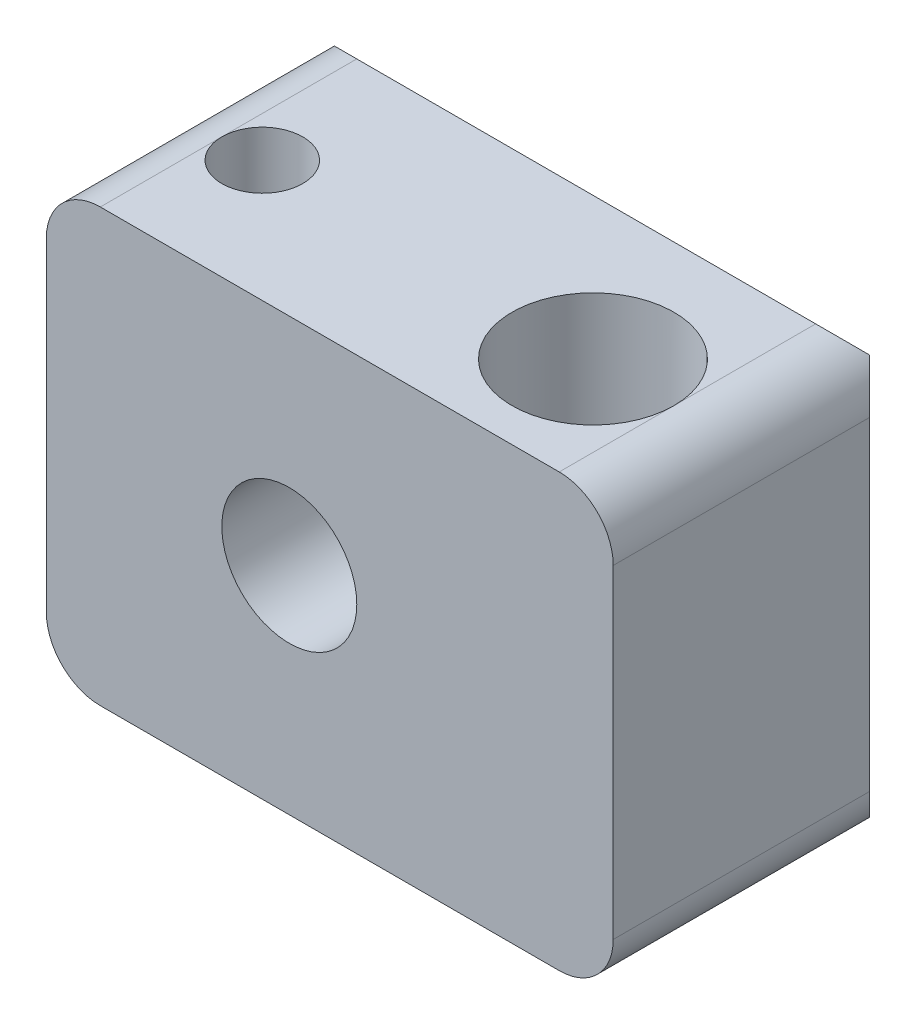
SolidWorks part; units mm, degrees
ref_plane "Front Plane" through (0, 0, 0) normal (0, 0, 1) x (1, 0, 0)
ref_plane "Top Plane" through (0, 0, 0) normal (0, 1, 0) x (1, 0, 0)
ref_plane "Right Plane" through (0, 0, 0) normal (1, 0, 0) x (0, 0, -1)
ref_plane "Plane1" through (0, 0, 0) normal (0, 0, -1) x (-1, 0, 0)
sketch "Sketch1" plane through (0, 0, 0) normal (0, 0, -1) x (-1, 0, 0)
  line L0 (10.5, 8) -> (-10.5, 8)
  line L1 (-10.5, -8) -> (10.5, -8)
  line L2 (10.5, 8) -> (10.5, -8)
  line L3 (-10.5, 8) -> (-10.5, -8)
  line L4 (10.5, 0) -> (-10.5, 0) construction
  line L5 (0, -8) -> (0, 8) construction
  point P8 (0, 0)
  dimension "D1" = 16
  dimension "D2" = 21
extrude "Boss-Extrude1" add sketch "Sketch1" against normal blind 11.5
sketch "Sketch2" plane through (0, 0, 0) normal (0, 0, -1) x (-1, 0, 0)
  line L0 (-4, 8) -> (-4, 6)
  line L1 (-4, 6) -> (8.3057, 6)
  line L2 (6.75, 8) -> (-4, 8)
  arc A0 (8.3057, 6) -> (6.75, 8) centre (-1.4712, 0) ccw
extrude "Cut-Extrude1" [suppressed] cut sketch "Sketch2" against normal blind 5
sketch "Sketch3" plane through (0, 0, 0) normal (0, 0, -1) x (-1, 0, 0)
  line L0 (8.3057, -6) -> (-4, -6)
  line L1 (-4, -6) -> (-4, -8)
  line L2 (-4, -8) -> (6.75, -8)
  arc A0 (6.75, -8) -> (8.3057, -6) centre (-1.4712, 0) ccw
extrude "Cut-Extrude2" [suppressed] cut sketch "Sketch3" against normal blind 5
hole_wizard "#10 Clearance Hole1" positions "Sketch5" profile "Sketch4" hole size "#10" standard "ANSI Inch"
sketch "Sketch5" plane through (0, 0, 11.5) normal (0, 0, 1) x (1, 0, 0)
  line L0 (10.5, 8) -> (10.5, -8) construction
  point P0 (-1.5, 0)
  dimension "D1" = 12
sketch "Sketch4" plane through (-1.5, 0, 11.5) normal (1, 0, 0) x (0, -1, 0)
  line L0 (0, 0) -> (0, 11.5)
  line L1 (0, 11.5) -> (2.5, 11.5)
  line L2 (2.5, 11.5) -> (2.5, 0)
  line L5 (2.5, 0) -> (0, 0)
  line L11 (0, -6.35) -> (0, 107.95) construction
  dimension "Thru Hole Dia." = 5
  dimension "Thru Hole Depth" = 11.5
hole_wizard "#3 Clearance Hole1" [suppressed] positions "Sketch7" profile "Sketch6" hole size "#3" standard "ANSI Inch"
sketch "Sketch7" plane through (0, 0, 11.5) normal (0, 0, 1) x (1, 0, 0)
  point P0 (0, 6)
  point P1 (0, -6)
sketch "Sketch6" plane through (0, 6, 11.5) normal (1, 0, 0) x (0, -1, 0)
  line L0 (0, 0) -> (0, 11.5)
  line L1 (0, 11.5) -> (1.5, 11.5)
  line L2 (1.5, 11.5) -> (1.5, 0)
  line L5 (1.5, 0) -> (0, 0)
  line L11 (0, -6.35) -> (0, 107.95) construction
  dimension "Thru Hole Dia." = 3
  dimension "Thru Hole Depth" = 11.5
hole_wizard "#12 Clearance Hole1" positions "Sketch9" profile "Sketch8" hole size "#12" standard "ANSI Inch" end condition through all
sketch "Sketch9" plane through (0, 8, 0) normal (0, 1, 0) x (1, 0, 0)
  line L0 (10.5, -11.5) -> (10.5, 0) construction
  point P0 (5.5, -7.25)
  dimension "D1" = 5
sketch "Sketch8" plane through (5.5, 8, 7.25) normal (1, 0, 0) x (0, 0, 1)
  line L0 (0, 0) -> (0, 16)
  line L1 (0, 16) -> (3, 16)
  line L2 (3, 16) -> (3, 0)
  line L5 (3, 0) -> (0, 0)
  line L11 (0, -6.35) -> (0, 107.95) construction
  dimension "Thru Hole Dia." = 6
  dimension "Thru Hole Depth" = 16
hole_wizard "#2 Clearance Hole1" positions "Sketch11" profile "Sketch10" hole size "#2" standard "ANSI Inch"
sketch "Sketch11" plane through (0, 0, 0) normal (0, 0, -1) x (-1, 0, 0)
  line L0 (-10.5, 8) -> (-10.5, -8) construction
  point P0 (-5.5, 0)
  dimension "D1" = 5
sketch "Sketch10" plane through (5.5, 0, 0) normal (1, 0, 0) x (0, 1, 0)
  line L0 (0, 0) -> (0, 4.25)
  line L1 (0, 4.25) -> (1.25, 4.25)
  line L2 (1.25, 4.25) -> (1.25, 0)
  line L5 (1.25, 0) -> (0, 0)
  line L11 (0, -6.35) -> (0, 107.95) construction
  dimension "Thru Hole Dia." = 2.5
  dimension "Thru Hole Depth" = 4.25
hole_wizard "#3 Clearance Hole2" positions "Sketch13" profile "Sketch12" hole size "#3" standard "ANSI Inch"
sketch "Sketch13" plane through (0, -8, 0) normal (0, -1, 0) x (-1, 0, 0)
  line L0 (10.5, -11.5) -> (10.5, 0) construction
  point P0 (7, -7)
  dimension "D1" = 3.5
sketch "Sketch12" plane through (-7, -8, 7) normal (1, 0, 0) x (0, 0, -1)
  line L0 (0, 0) -> (0, 16)
  line L1 (0, 16) -> (1.5, 16)
  line L2 (1.5, 16) -> (1.5, 0)
  line L5 (1.5, 0) -> (0, 0)
  line L11 (0, -6.35) -> (0, 107.95) construction
  dimension "Thru Hole Dia." = 3
  dimension "Thru Hole Depth" = 16
hole_wizard "#2 Clearance Hole2" positions "Sketch15" profile "Sketch14" hole size "#2" standard "ANSI Inch"
sketch "Sketch15" plane through (0, 0, 0) normal (0, 0, -1) x (-1, 0, 0)
  line L0 (10.5, -8) -> (10.5, 8) construction
  point P0 (7, 0)
  dimension "D1" = 3.5
sketch "Sketch14" plane through (-7, 0, 0) normal (1, 0, 0) x (0, 1, 0)
  line L0 (0, 0) -> (0, 5.5)
  line L1 (0, 5.5) -> (1.25, 5.5)
  line L2 (1.25, 5.5) -> (1.25, 0)
  line L5 (1.25, 0) -> (0, 0)
  line L11 (0, -6.35) -> (0, 107.95) construction
  dimension "Thru Hole Dia." = 2.5
  dimension "Thru Hole Depth" = 5.5
chamfer "Chamfer2" distance 2 4 edges at (10.5, 0, 0) (0, -8, 0) (-10.5, 0, 0) (0, 8, 0)
fillet "Fillet1" radius 2 4 edges at (10.5, 8, 6.75) (10.5, -8, 6.75) (-10.5, -8, 6.75) (-10.5, 8, 6.75)
